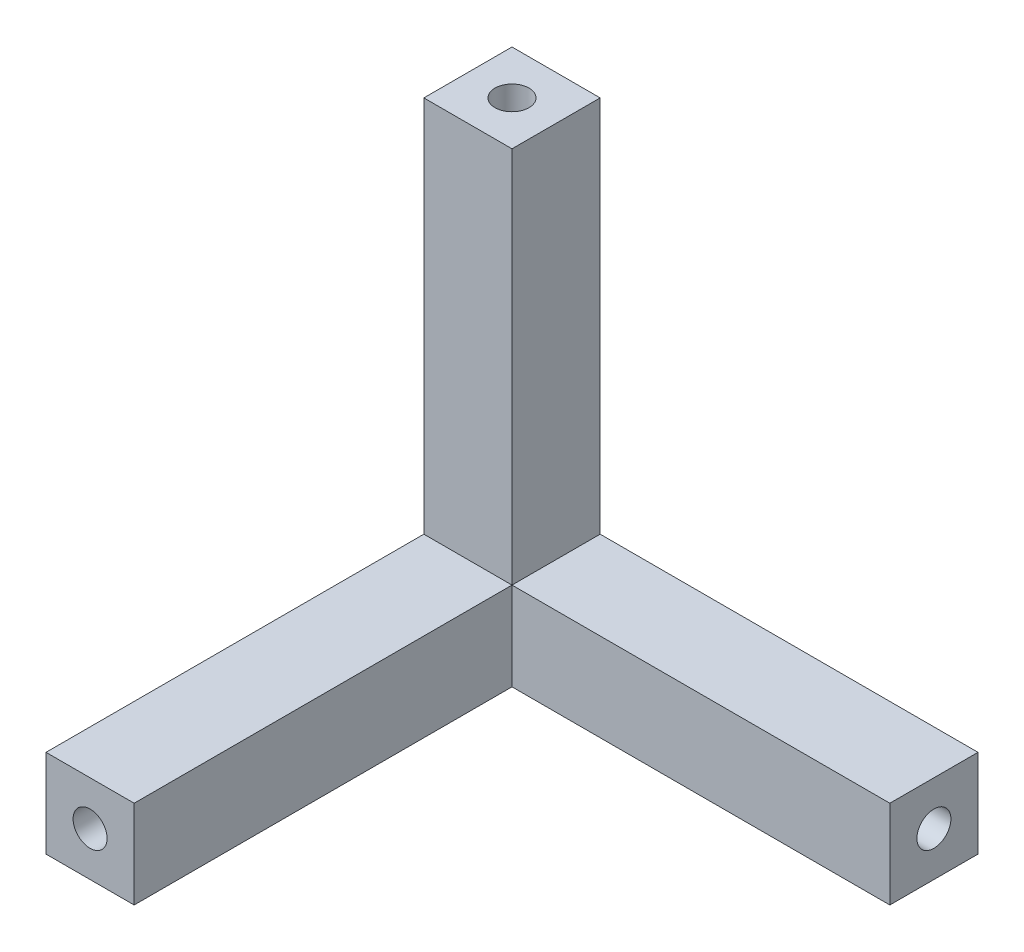
SolidWorks part; units mm, degrees
ref_plane "Front Plane" through (0, 0, 0) normal (0, 0, 1) x (1, 0, 0)
ref_plane "Top Plane" through (0, 0, 0) normal (0, 1, 0) x (1, 0, 0)
ref_plane "Right Plane" through (0, 0, 0) normal (1, 0, 0) x (0, 0, -1)
sketch "Sketch2" plane through (0, 0, 0) normal (0, 1, 0) x (1, 0, 0)
  line L0 (-1.75, 1.75) -> (-1.75, -16.75)
  line L1 (-1.75, 1.75) -> (16.75, 1.75)
  line L2 (16.75, 1.75) -> (16.75, -1.75)
  line L3 (16.75, -1.75) -> (1.75, -1.75)
  line L4 (1.75, -1.75) -> (1.75, -16.75)
  line L5 (1.75, -16.75) -> (-1.75, -16.75)
  point P2 (16.75, 0)
  point P7 (0, -16.75)
  dimension "D1" = 15
  dimension "D2" = 3.5
extrude "Boss-Extrude1" add sketch "Sketch2" along normal mid plane 3.5
sketch "Sketch3" plane through (0, 0, 16.75) normal (0, 0, 1) x (1, 0, 0)
  circle A0 centre (0, 0) radius 0.675
  dimension "D1" = 1.35
extrude "Cut-Extrude1" cut sketch "Sketch3" against normal blind 15
sketch "Sketch4" plane through (16.75, 0, 0) normal (1, 0, 0) x (0, 0, -1)
  circle A0 centre (0, 0) radius 0.675
  dimension "D1" = 1.35
extrude "Cut-Extrude2" cut sketch "Sketch4" against normal blind 15
sketch "Sketch5" plane through (0, 1.75, 0) normal (0, 1, 0) x (1, 0, 0)
  line L1 (1.75, -1.75) -> (-1.75, -1.75)
  line L2 (1.75, -1.75) -> (1.75, 1.75)
  line L3 (1.75, 1.75) -> (-1.75, 1.75)
  line L4 (-1.75, -1.75) -> (-1.75, 1.75)
ref_plane "Plane1" through (0, 0, 0) normal (-0.7071, 0, 0.7071) x (0.7071, 0, 0.7071)
sketch "Sketch7" plane through (0, 0, 0) normal (-0.7071, 0, 0.7071) x (0.7071, 0, 0.7071)
  line L0 (0, 1.75) -> (0, 16.75)
  line L1 (0, 1.75) -> (-2.4749, 1.75) construction
  line L2 (-2.4749, 1.75) -> (10.6066, 1.75) construction
  point P6 (0, 0)
  dimension "D1" = 90
  dimension "D2" = 15
sweep "Sweep1" add profiles "Sketch5" path "Sketch7"
sweep "Cut-Sweep1" cut path "Sketch7<2>" circular profile diameter 1.35 parameters "D3"=1.35
sketch "Sketch7<2>" plane through (0, 0, 0) normal (-0.7071, 0, 0.7071) x (0.7071, 0, 0.7071) same geometry as "Sketch7"
